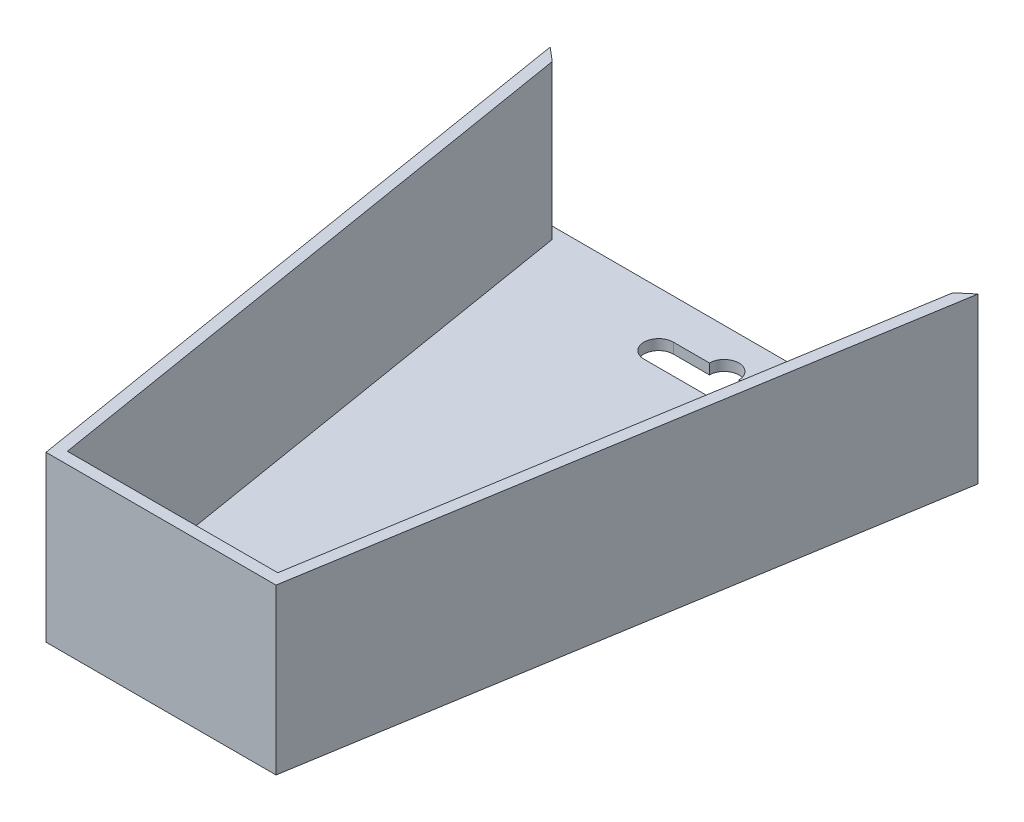
SolidWorks part; units mm, degrees
ref_plane "Front Plane" through (0, 0, 0) normal (0, 0, 1) x (1, 0, 0)
ref_plane "Top Plane" through (0, 0, 0) normal (0, 1, 0) x (1, 0, 0)
ref_plane "Right Plane" through (0, 0, 0) normal (1, 0, 0) x (0, 0, -1)
sketch "Sketch1" plane through (0, 0, 0) normal (0, 1, 0) x (1, 0, 0)
  line L0 (-46.99, 0) -> (46.99, 0)
  line L1 (-25.2666, -132.4864) -> (25.2666, -132.4864)
  line L2 (-46.99, 0) -> (-25.2666, -132.4864)
  line L3 (46.99, 0) -> (25.2666, -132.4864)
  line L4 (-11.1633, -8.7738) -> (-3.2331, -8.7738)
  line L5 (-11.1633, -15.24) -> (11.1633, -15.24)
  line L6 (3.2331, -8.7738) -> (11.1633, -8.7738)
  line L7 (-43.9996, -2.54) -> (43.9996, -2.54)
  line L8 (43.9996, -2.54) -> (23.1092, -129.9464)
  line L9 (-23.1092, -129.9464) -> (23.1092, -129.9464)
  line L10 (-43.9996, -2.54) -> (-23.1092, -129.9464)
  line L11 (-46.99, 0) -> (-43.9996, -2.54)
  line L12 (43.9996, -2.54) -> (46.99, 0)
  arc A0 (-11.1633, -15.24) -> (-11.1633, -8.7738) centre (-11.1633, -12.0069) cw
  arc A1 (11.1633, -8.7738) -> (11.1633, -15.24) centre (11.1633, -12.0069) cw
  arc A2 (3.2331, -8.7738) -> (-3.2331, -8.7738) centre (0, -8.7738) ccw
  point P4 (0, -132.4864)
  point P5 (0, 0)
  point P16 (0, -15.24)
  point P21 (0, 0)
  dimension "D4" = 22.3266
  dimension "D5" = 3.2331
  dimension "D1" = 93.98
  dimension "D2" = 50.5333
  dimension "D3" = 132.4864
  dimension "D6" = 15.24
  dimension "D7" = 2.54
extrude "Base" add sketch "Sketch1" along normal blind 2.286 contours L6 A2 L4 A0 L5 A1 | L2 L1 L3 L0 region at (0, 0, 11.6164)
extrude "Walls" add sketch "Sketch1<4>" along normal blind 36.1315 contours L12 L8 L9 L10 L11 L2 L1 L3 region at (-46.5464, 0, 2.508)
sketch "Sketch1<4>" plane through (0, 0, 0) normal (0, 1, 0) x (1, 0, 0) same geometry as "Sketch1"
